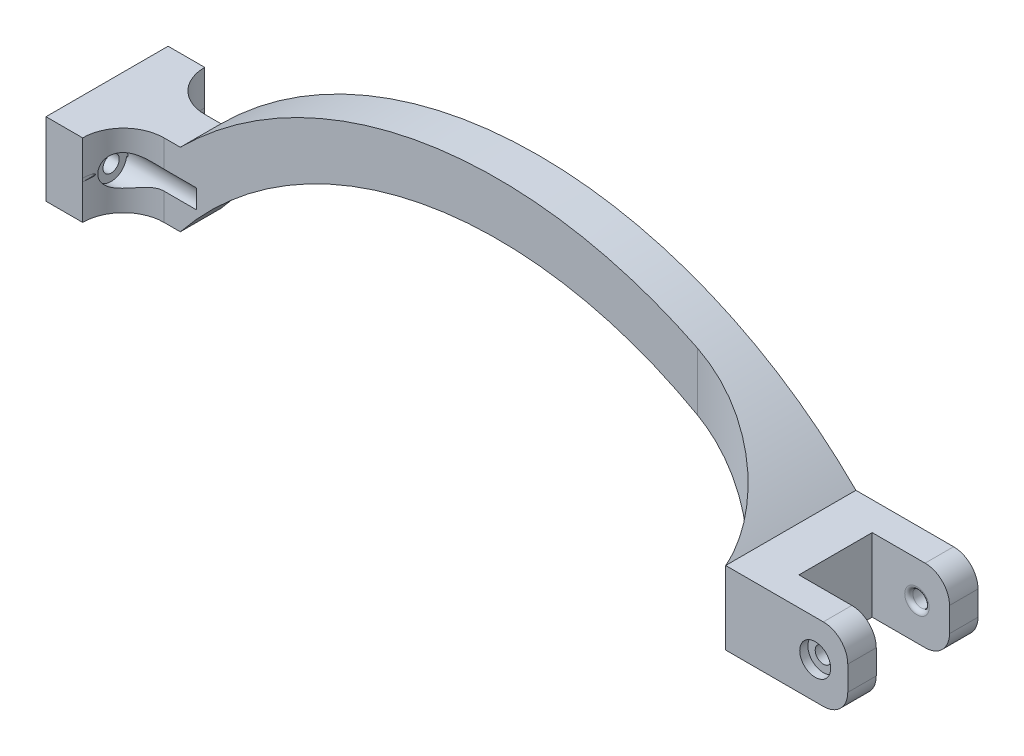
SolidWorks part; units mm, degrees
note: The reader was unsure of these and kept them because the rebuilt part matched: shared geometry of "Sketch6<2>".
ref_plane "Front Plane" through (0, 0, 0) normal (0, 0, 1) x (1, 0, 0)
ref_plane "Top Plane" through (0, 0, 0) normal (0, 1, 0) x (1, 0, 0)
ref_plane "Right Plane" through (0, 0, 0) normal (1, 0, 0) x (0, 0, -1)
sketch "Sketch1" plane through (0, 0, 0) normal (0, 0, 1) x (1, 0, 0)
  line L0 (0, 0) -> (90, 0) construction
  line L1 (90, 4.5) -> (85, 4.5)
  line L3 (90, 4.5) -> (90, -4.5)
  line L4 (0, 4.5) -> (7, 4.5)
  line L5 (0, -4.5) -> (7, -4.5)
  circle A0 centre (0, 0) radius 0.2
  arc A1 (7, 4.5) -> (85, 4.5) centre (46, -34.5) cw
  circle A2 centre (0, 0) radius 4.5
  arc A3 (7, -4.5) -> (85, -4.5) centre (46, -35.789) cw
  dimension "D2" = 9
  dimension "D1" = 90
extrude "Boss-Extrude1" add sketch "Sketch1" along normal blind 5
sketch "Sketch3" plane through (0, 0, 5) normal (0, 0, 1) x (1, 0, 0)
  line L0 (90, 0) -> (90, -4.5)
  line L1 (90, -4.5) -> (85, -4.5)
  line L2 (85, -4.5) -> (80.9163, 0)
  line L3 (80.9163, 0) -> (90, 0)
extrude "Boss-Extrude2" add sketch "Sketch3" against normal blind 5
sketch "Sketch4" plane through (0, 4.5, 0) normal (0, 1, 0) x (1, 0, 0)
  line L1 (90, -5) -> (85, -5) construction
  line L2 (100, -3.5) -> (90.5, -3.5)
  line L3 (90, 0) -> (100, 0)
  line L4 (90, 0) -> (90, -16)
  line L5 (90, -16) -> (100, -16)
  line L6 (100, 0) -> (100, -16)
  line L7 (90, 0) -> (100, -16) construction
  line L8 (90, -16) -> (100, 0) construction
  line L9 (90.5, -3.5) -> (90.5, -12.5)
  line L10 (90.5, -12.5) -> (100, -12.5)
  point P4 (95, -8)
  line M11 (90, -5) -> (90, 0)
  dimension "D1" = 10
  dimension "D2" = 9.5
  dimension "D3" = 9
  dimension "D4" = 16
  dimension "D5" = 3.5
  dimension "D6" = 3
extrude "Boss-Extrude3" add sketch "Sketch4" against normal blind 9 contours L10 L9 L2 L6 L3 L4 L5 M11
sketch "Sketch5" plane through (0, 0, 0) normal (0, 0, -1) x (-1, 0, 0)
  line L0 (-100, -4.5) -> (-100, 4.5) construction
  line L1 (-85, 4.5) -> (-100, 4.5) construction
  circle A0 centre (-96, 0) radius 1
  dimension "D1" = 4
  dimension "D2" = 4.5
extrude "Cut-Extrude1" cut sketch "Sketch5" against normal blind 16
sketch "Sketch6" plane through (0, 0, 0) normal (0, 0, -1) x (-1, 0, 0)
  circle A0 centre (-96, 0) radius 1.9
extrude "Cut-Extrude2" cut sketch "Sketch6" against normal blind 1
fillet "Fillet1" radius 0.5 1 edges at (97, 0, 12.5)
sketch "Sketch7" plane through (0, -4.5, 0) normal (0, -1, 0) x (1, 0, 0)
  line L1 (90, 5) -> (85, 5)
  line L2 (90, 5) -> (90, 16)
  line L3 (90, 16) -> (85, 16)
  line L4 (85, 5) -> (85, 16)
extrude "Boss-Extrude4" add sketch "Sketch7" against normal blind 9
fillet "Fillet2" radius 15 1 edges at (85, 0, 5)
fillet "Fillet3" radius 0.5 1 edges at (95, 0, 3.5)
extrude "Cut-Extrude3" cut sketch "Sketch6<2>" along normal blind 1 from offset 16 offset against normal yes
sketch "Sketch6<2>" plane through (0, 0, 0) normal (0, 0, -1) x (-1, 0, 0) same geometry as "Sketch6"
fillet "Fillet4" radius 3 4 edges at (100, -4.5, 14.25) (100, 4.5, 1.75) (100, -4.5, 1.75) (100, 4.5, 14.25)
sketch "Sketch8" plane through (0, 4.5, 0) normal (0, 1, 0) x (1, 0, 0)
  line L0 (0, -5) -> (0, 0) construction
  line L1 (-4.5, 5) -> (0, 5)
  line L2 (-4.5, 5) -> (-4.5, -10)
  line L3 (-4.5, -10) -> (0, -10)
  line L4 (0, 5) -> (0, -10)
  line L5 (-4.5, 5) -> (0, -10) construction
  line L6 (-4.5, -10) -> (0, 5) construction
  point P0 (-2.25, -2.5)
  dimension "D1" = 4.5
  dimension "D2" = 2.25
  dimension "D3" = 15
extrude "Boss-Extrude5" add sketch "Sketch8" against normal blind 9 from offset 0
sketch "Sketch9" plane through (-4.5, 0, 0) normal (-1, 0, 0) x (0, 0, 1)
  line L0 (-5, -4.5) -> (-5, 4.5) construction
  line L1 (10, -4.5) -> (10, 4.5) construction
  line L2 (-5, 4.5) -> (10, 4.5) construction
  circle A0 centre (-1.5, 0) radius 1
  circle A1 centre (6.5, 0) radius 1
  dimension "D1" = 3.5
  dimension "D2" = 3.5
  dimension "D3" = 4.5
  dimension "D4" = 4.5
fillet "Fillet5" radius 5 2 edges at (0, -2.35, 5) (0, -2.35, 0)
extrude "Cut-Extrude4" cut sketch "Sketch9" against normal blind 9
sketch "Sketch10" plane through (-4.5, 0, 0) normal (-1, 0, 0) x (0, 0, 1)
  circle A0 centre (-1.5, 0) radius 1.9
  circle A1 centre (6.5, 0) radius 1.9
extrude "Cut-Extrude5" cut sketch "Sketch10" against normal blind 9 from offset 4.5
